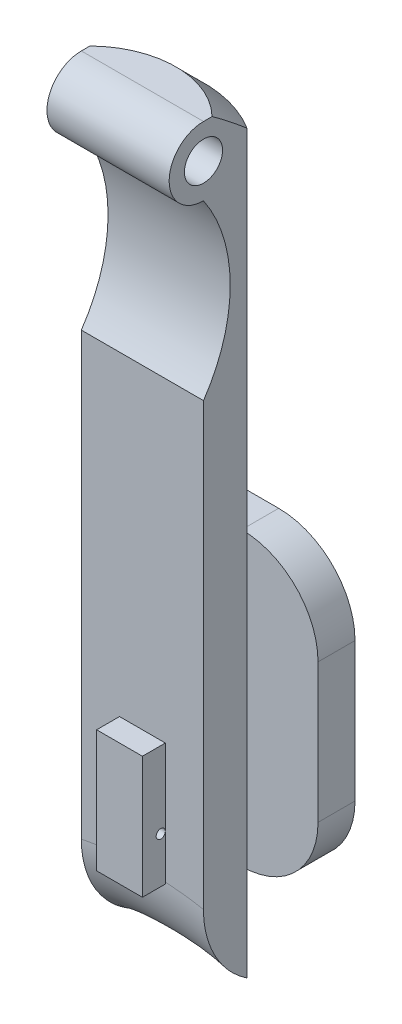
SolidWorks part; units mm, degrees
material "CA"
ref_plane "Alzado" through (0, 0, 0) normal (0, 0, 1) x (1, 0, 0)
ref_plane "Planta" through (0, 0, 0) normal (0, 1, 0) x (1, 0, 0)
ref_plane "Vista lateral" through (0, 0, 0) normal (1, 0, 0) x (0, 0, -1)
sketch "Croquis2" plane through (0, 0, 0) normal (0, 1, 0) x (1, 0, 0)
  line L2 (-4, 3.5) -> (-4, 6.3443)
  line L4 (4, 3.5) -> (4, 6.3443)
  line L5 (0, 0) -> (4, 6.3443) construction
  line L6 (-4, 6.3443) -> (0, 0) construction
  line L7 (4, 3.5) -> (-4, 3.5)
  arc A1 (4, 6.3443) -> (-4, 6.3443) centre (0, 0) ccw
  point P12 (0, 3.5)
  dimension "D2" = 8
  dimension "D3" = 3.5
  dimension "D4" = 2.8443
extrude "Saliente-Extruir1" add sketch "Croquis2" along normal blind 50
fillet "Redondeo1" radius 6 1 edges at (0, 0, -3.5)
sketch "Croquis3" plane through (4, 0, 0) normal (1, 0, 0) x (0, 0, -1)
  line L0 (3.5, 50) -> (3.5, 5.3025) construction
  circle A0 centre (3.5, 47.75) radius 2.25
  circle A1 centre (3.5, 47.75) radius 1.25
  dimension "D1" = 2.5
  dimension "D2" = 1
extrude "Saliente-Extruir2" add sketch "Croquis3" against normal up to surface (8 mm away) up to face at (-4, 26.1091, -4.8336)
sketch "Croquis4" plane through (4, 0, 0) normal (1, 0, 0) x (0, 0, -1)
  line L0 (3.5, 49) -> (3.5, 46.5) construction
  circle A0 centre (3.5, 47.75) radius 1.25
extrude "Cortar-Extruir1" cut sketch "Croquis4" against normal blind 8
chamfer "Chaflán1" distance 1.8 angle 45 1 edges at (0, 50, -7.5)
sketch "Croquis5" plane through (0, 0, -3.5) normal (0, 0, 1) x (1, 0, 0)
  line L1 (-1.5, 13.5) -> (1.5, 13.5)
  line L2 (-1.5, 13.5) -> (-1.5, 5.5)
  line L3 (-1.5, 5.5) -> (1.5, 5.5)
  line L4 (1.5, 13.5) -> (1.5, 5.5)
  line L5 (-1.5, 13.5) -> (1.5, 5.5) construction
  line L6 (-1.5, 5.5) -> (1.5, 13.5) construction
  point P0 (0, 9.5)
  dimension "D1" = 3
  dimension "D2" = 8
  dimension "D3" = 0
  dimension "D4" = 13.5
extrude "Saliente-Extruir3" add sketch "Croquis5" along normal blind 1.5
sketch "Croquis6" plane through (-1.5, 0, 0) normal (-1, 0, 0) x (0, 0, 1)
  line L0 (-3.5, 13.5) -> (-3.5, 5.6139) construction
  line L1 (-2, 5.5) -> (-3.5, 5.5) construction
  circle A0 centre (-3.2, 8.5) radius 0.3
  dimension "D1" = 0.6
  dimension "D2" = 0.3
  dimension "D3" = 3
extrude "Cortar-Extruir2" cut sketch "Croquis6" against normal blind 3
sketch "Croquis7" plane through (0, 0, 0) normal (1, 0, 0) x (0, 0, -1)
  line L0 (7.5, 5) -> (9.9223, 5)
  line L1 (9.9223, 5) -> (9.9223, 24.1)
  line L5 (7.5, 5) -> (7.5, 24.1)
  line L6 (7.5, 0) -> (7.5, 48.2) construction
  line L7 (7.5, 24.1) -> (9.9223, 24.1)
  dimension "D1" = 5
  dimension "D2" = 2.4223
extrude "Saliente-Extruir4" add sketch "Croquis7" along normal blind 7.5 and the other way blind 7.5 separate body
fillet "Redondeo2" radius 5 4 edges at (-7.5, 24.1, -8.7112) (-7.5, 5, -8.7112) (7.5, 5, -8.7112) (7.5, 24.1, -8.7112)
sketch "Sketch1" plane through (4, 0, 0) normal (1, 0, 0) x (0, 0, -1)
  line L0 (3.5, 45.5) -> (3.5, 5.3025) construction
  line L1 (3.5, 45.5) -> (3.5, 34.1684)
  arc A1 (3.5, 45.5) -> (3.5, 34.1684) centre (-4.7955, 39.8342) cw
extrude "Cut-Extrude1" cut sketch "Sketch1" against normal up to surface (8 mm away) up to face at (-4, 33.1728, -3.9173)
